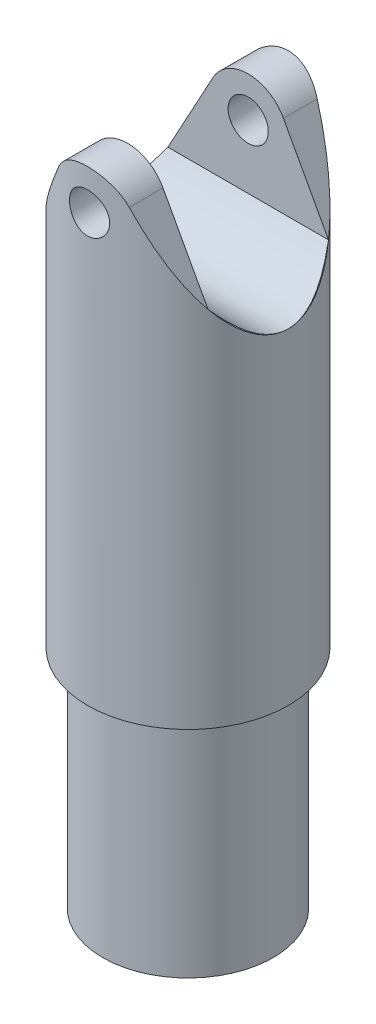
SolidWorks part; units mm, degrees
ref_plane "前视基准面" through (0, 0, 0) normal (0, 0, 1) x (1, 0, 0)
ref_plane "上视基准面" through (0, 0, 0) normal (0, 1, 0) x (1, 0, 0)
ref_plane "右视基准面" through (0, 0, 0) normal (1, 0, 0) x (0, 0, -1)
other "Configuration Table"
sketch "草图1" plane through (0, 0, 0) normal (0, 1, 0) x (1, 0, 0)
  circle A0 centre (0, 0) radius 17
extrude "凸台-拉伸1" add sketch "草图1" along normal blind 45
sketch "草图2" plane through (0, 45, 0) normal (0, 1, 0) x (1, 0, 0)
  circle A0 centre (0, 0) radius 20
extrude "凸台-拉伸2" add sketch "草图2" along normal blind 95
sketch "草图8" plane through (0, 0, 0) normal (0, 0, 1) x (1, 0, 0)
  line L0 (-20, 110) -> (-7.0259, 133.8259)
  line L2 (-20, 140) -> (-20, 45) construction
  line L4 (20, 45) -> (20, 140) construction
  line L5 (20, 110) -> (7.0259, 133.8259)
  line L6 (-20, 140) -> (-20, 110)
  line L7 (-20, 140) -> (20, 140)
  line L8 (20, 140) -> (20, 110)
  arc A0 (7.0259, 133.8259) -> (-7.0259, 133.8259) centre (0, 130) ccw
  point P0 (0, 130)
extrude "切除-拉伸3" cut sketch "草图8" against normal mid plane 40
sketch "草图9" plane through (0, 0, 0) normal (0, 0, 1) x (1, 0, 0)
  circle A0 centre (0, 130) radius 4
  point P0 (0, 130)
extrude "切除-拉伸4" cut sketch "草图9" against normal mid plane 40
sketch "草图10" plane through (0, 0, 0) normal (1, 0, 0) x (0, 0, -1)
  line L0 (0, 138) -> (12, 138)
  line L1 (20, 138) -> (-20, 138) construction
  line L2 (12, 138) -> (12, 117.3456)
  line L4 (-12, 117.3456) -> (-12, 138)
  line L5 (-12, 138) -> (0, 138)
  ellipse E0 centre (0, 146.7282) end of major axis (0, 110) minor radius 20 (-18.7253, 133.8259) -> (18.7253, 133.8259) ccw construction
  spline S0 degree 2 poles (-12, 117.3456) (0, 102.6544) (12, 117.3456) knots 0 0 0 1 1 1
extrude "切除-拉伸5" cut sketch "草图10" against normal mid plane 40
